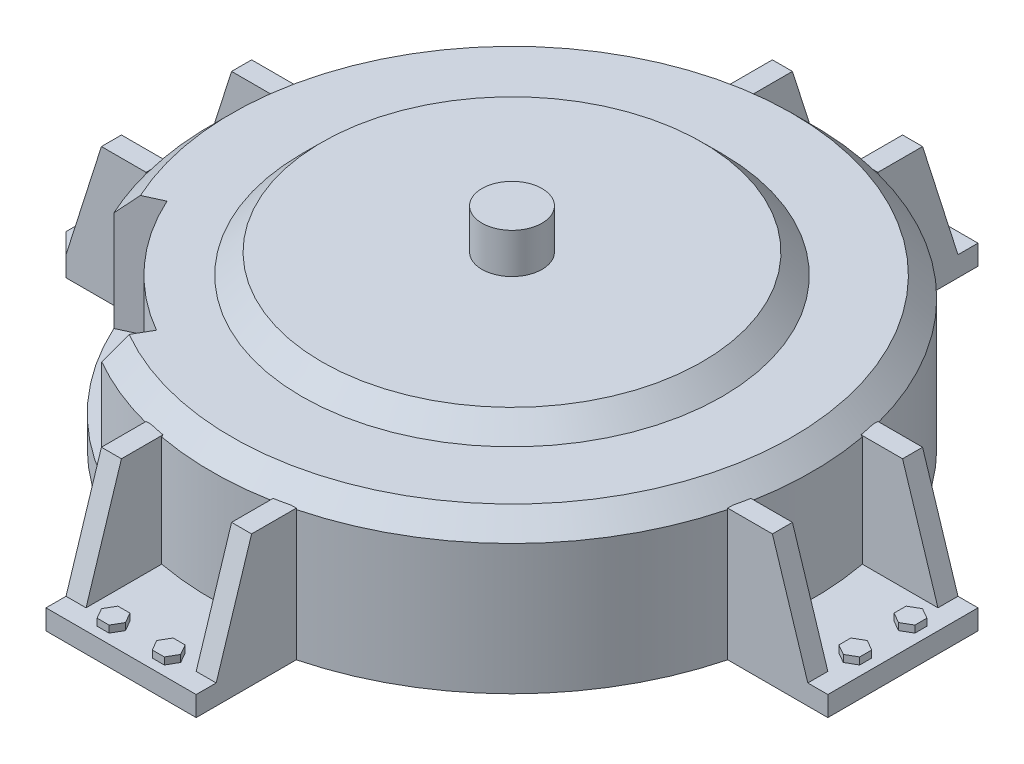
SolidWorks part; units mm, degrees
ref_plane "Front Plane" through (0, 0, 0) normal (0, 0, 1) x (1, 0, 0)
ref_plane "Top Plane" through (0, 0, 0) normal (0, 1, 0) x (1, 0, 0)
ref_plane "Right Plane" through (0, 0, 0) normal (1, 0, 0) x (0, 0, -1)
sketch "Sketch1" plane through (0, 0, 0) normal (0, 1, 0) x (1, 0, 0)
  circle A0 centre (0, 0) radius 150
  dimension "D1" = 300
extrude "Boss-Extrude1" add sketch "Sketch1" along normal blind 75
chamfer "Chamfer1" distance 10 angle 45 1 edges at (0, 75, 150)
sketch "Sketch2" plane through (0, 0, 0) normal (0, -1, 0) x (1, 0, 0)
  line L1 (-145.2369, 37.5) -> (-195.2369, 37.5)
  line L3 (-145.2369, -37.5) -> (-195.2369, -37.5)
  line L4 (-195.2369, 37.5) -> (-195.2369, -37.5)
  circle A0 centre (0, 0) radius 150 construction
  circle A1 centre (0, 0) radius 150
  point P0 (-150, 0)
  circle M4 centre (0, 0) radius 150
  dimension "D1" = 75
  dimension "D2" = 50
extrude "Boss-Extrude2" add sketch "Sketch2" against normal blind 10 contours L1 L4 L3 M4 region at (-171.8083, 0, 0)
chamfer "Chamfer2" distance 10 angle 45 2 edges at (-195.2369, 5, -37.5) (-195.2369, 5, 37.5)
sketch "Sketch3" plane through (0, 0, 37.5) normal (0, 0, 1) x (1, 0, 0)
  line L0 (-145.2369, 10) -> (-145.2369, 65.626)
  line L1 (-145.2369, 65.626) -> (-167.5569, 65.626)
  line L2 (-167.5569, 65.626) -> (-185.2369, 10)
  line L3 (-145.2369, 10) -> (-185.2369, 10) construction
  line L4 (-185.2369, 10) -> (-145.2369, 10)
  line L5 (-185.2369, 10) -> (-185.2369, 0) construction
  dimension "D1" = 17.68
  dimension "D2" = 55.626
extrude "Boss-Extrude3" add sketch "Sketch3" against normal blind 10
sketch "Sketch4" plane through (0, 10, 0) normal (0, 1, 0) x (1, 0, 0)
  line L0 (-185.2369, 37.5) -> (-185.2369, -46.4272) construction
  line L2 (-180.0407, -16.782) -> (-180.0407, -10.782)
  line L3 (-180.0407, -10.782) -> (-185.2369, -7.782)
  line L4 (-185.2369, -7.782) -> (-190.433, -10.782)
  line L5 (-190.433, -10.782) -> (-190.433, -16.782)
  line L6 (-190.433, -16.782) -> (-185.2369, -19.782)
  line L7 (-185.2369, -19.782) -> (-180.0407, -16.782)
  circle A0 centre (-185.2369, -13.782) radius 5.1962 construction
  dimension "D1" = 6
extrude "Boss-Extrude4" add sketch "Sketch4" along normal blind 3.5
mirror "Mirror1" about plane through (0, 0, 0) normal (0, 0, 1) of "Boss-Extrude4", "Boss-Extrude3"
pattern_circular "CirPattern1" count 4 over 360 about axis through (0, 0, 0) along (0, 1, 0) of "Boss-Extrude2", "Boss-Extrude3", "Mirror1"
sketch "Sketch5" plane through (0, 75, 0) normal (0, 1, 0) x (1, 0, 0)
  line L2 (-118.1912, -54.1371) -> (-136.3745, -62.4659)
  line L3 (-65, -112.5833) -> (-75, -129.9038)
  arc A0 (-118.1912, -54.1371) -> (-65, -112.5833) centre (0, 0) ccw
  arc A1 (-145.2369, -37.5) -> (-37.5, -145.2369) centre (0, 0) ccw construction
  arc A2 (-136.3745, -62.4659) -> (-75, -129.9038) centre (0, 0) ccw
extrude "Cut-Extrude1" cut sketch "Sketch5" against normal blind 60
sketch "Sketch6" plane through (0, 75, 0) normal (0, 1, 0) x (1, 0, 0)
  circle A0 centre (0, 0) radius 110
  dimension "D1" = 220
extrude "Boss-Extrude5" add sketch "Sketch6" along normal blind 10
chamfer "Chamfer3" distance 15 angle 45 1 edges at (0, 85, 110)
sketch "Sketch7" plane through (0, 85, 0) normal (0, 1, 0) x (1, 0, 0)
  circle A0 centre (0, 0) radius 15
  dimension "D1" = 30
extrude "Boss-Extrude6" add sketch "Sketch7" along normal blind 20
